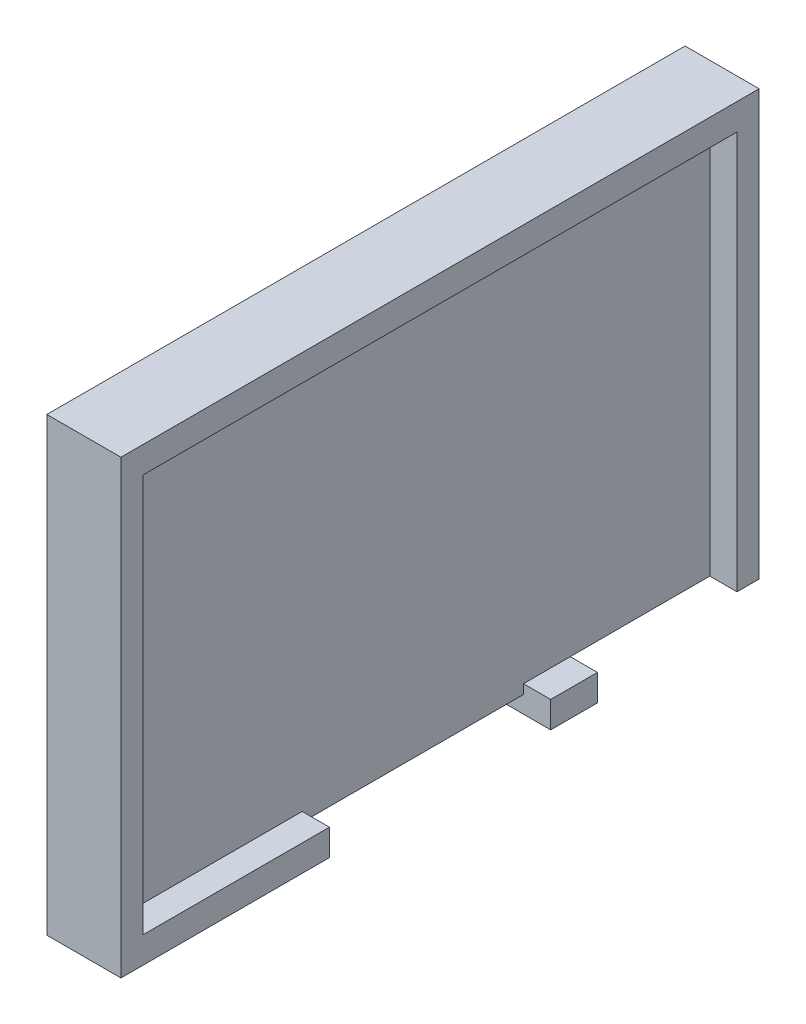
SolidWorks part; units mm, degrees
ref_plane "Front Plane" through (0, 0, 0) normal (1, 0, 0) x (0, 1, 0)
ref_plane "Top Plane" through (0, 0, 0) normal (0, 0, 1) x (0, 1, 0)
ref_plane "Right Plane" through (0, 0, 0) normal (0, 1, 0) x (-1, 0, 0)
sketch "Sketch1" plane through (0, 0, 0) normal (1, 0, 0) x (0, 1, 0)
  line L0 (42.12, 117.43) -> (42.12, 129.18) construction
  line L1 (44.62, 126.68) -> (71.12, 126.68)
  line L2 (44.62, 126.68) -> (44.62, 89.18)
  line L3 (44.62, 89.18) -> (71.12, 89.18)
  line L4 (71.12, 126.68) -> (71.12, 89.18)
  line L5 (42.12, 129.18) -> (89.12, 129.18) construction
  dimension "D1" = 26.5
  dimension "D2" = 37.5
  dimension "D3" = 2.5
  dimension "D4" = 2.5
extrude "Boss-Extrude1" add sketch "Sketch1" along normal blind 4.353 contours L2 L3 L4 L1
sketch "Sketch2" plane through (4.353, 0, 0) normal (1, 0, 0) x (0, 1, 0)
  line L0 (57.87, 126.68) -> (57.87, 89.18)
  line L1 (44.62, 126.68) -> (71.12, 126.68) construction
  line L2 (44.62, 89.18) -> (71.12, 89.18) construction
  line L3 (44.62, 107.93) -> (71.12, 107.93)
  line L4 (44.62, 126.68) -> (44.62, 89.18) construction
  line L5 (71.12, 126.68) -> (71.12, 89.18) construction
  line L7 (69.57, 90.48) -> (46.17, 90.48)
  line L8 (69.57, 90.48) -> (69.57, 125.38)
  line L9 (69.57, 125.38) -> (46.17, 125.38)
  line L10 (46.17, 90.48) -> (46.17, 125.38)
  line L11 (69.57, 90.48) -> (46.17, 125.38) construction
  line L12 (69.57, 125.38) -> (46.17, 90.48) construction
  point P12 (57.87, 107.93)
  dimension "D1" = 23.4
  dimension "D2" = 34.9
extrude "Cut-Extrude1" cut sketch "Sketch2" against normal blind 1.6 contours L7 L10 L9 L8
sketch "Sketch3" plane through (4.353, 0, 0) normal (1, 0, 0) x (0, 1, 0)
  line L0 (44.62, 107.93) -> (46.17, 107.93)
  line L1 (44.62, 126.68) -> (44.62, 89.18) construction
  line L2 (46.17, 90.48) -> (46.17, 125.38) construction
  line L3 (46.17, 125.38) -> (46.17, 126.68)
  line L4 (44.62, 126.68) -> (71.12, 126.68) construction
  line L5 (45.395, 107.93) -> (45.395, 126.68)
  line L7 (46.17, 101.43) -> (44.62, 101.43)
  line L8 (46.17, 101.43) -> (46.17, 114.43)
  line L9 (46.17, 114.43) -> (44.62, 114.43)
  line L10 (44.62, 101.43) -> (44.62, 114.43)
  line L11 (46.17, 101.43) -> (44.62, 114.43) construction
  line L12 (46.17, 114.43) -> (44.62, 101.43) construction
  dimension "D1" = 13
extrude "Cut-Extrude2" cut sketch "Sketch3" against normal blind 1.6 contours L7 L10 L9 L8
sketch "Sketch4" plane through (0, 44.62, 0) normal (0, -1, 0) x (1, 0, 0)
  line L0 (0, 126.68) -> (0, 89.18) construction
  line L1 (2.753, 101.43) -> (0, 101.43)
  line L2 (2.753, 101.43) -> (2.753, 114.43)
  line L3 (2.753, 114.43) -> (0, 114.43)
  line L4 (0, 101.43) -> (0, 114.43)
extrude "Cut-Extrude3" cut sketch "Sketch4" against normal blind 1
sketch "Sketch5" plane through (4.353, 0, 0) normal (1, 0, 0) x (0, 1, 0)
  line L0 (46.17, 90.48) -> (46.17, 101.43) construction
  line L1 (44.62, 89.18) -> (46.17, 89.18)
  line L2 (44.62, 89.18) -> (44.62, 98.68)
  line L3 (44.62, 98.68) -> (46.17, 98.68)
  line L4 (46.17, 89.18) -> (46.17, 98.68)
  dimension "D1" = 9.5
extrude "Cut-Extrude5" cut sketch "Sketch5" against normal blind 1.6 contours L2 L1 L4 L3
sketch "Sketch6" plane through (0, 0, 89.18) normal (0, 0, -1) x (1, 0, 0)
  line L0 (4.353, -46.17) -> (1.953, -46.17)
  line L1 (1.953, -46.17) -> (1.953, -49.12)
  line L2 (1.953, -49.12) -> (0, -49.12)
  line L3 (0, -44.62) -> (0, -71.12) construction
  line L4 (0, -49.12) -> (0, -44.62)
  line L5 (0, -44.62) -> (2.753, -44.62)
  line L6 (2.753, -44.62) -> (2.753, -46.17)
  line M1 (2.753, -46.17) -> (2.753, -44.62)
  line M2 (2.753, -44.62) -> (0, -44.62)
  line M3 (0, -44.62) -> (0, -71.12)
  dimension "D1" = 2.4
  dimension "D2" = 2.95
extrude "Cut-Extrude6" cut sketch "Sketch6" against normal blind 9.5 contours L2 L1 L0 M1 M2 M3 region at (1.1467, 46.6876, 89.18)
sketch "Sketch7" plane through (0, 0, 0) normal (-1, 0, 0) x (0, -1, 0)
  line L0 (-49.12, 98.68) -> (-49.12, 89.18) construction
  line L1 (-66.8403, 98.7845) -> (-56.9188, 98.7845)
  line L2 (-66.8403, 98.7845) -> (-66.8403, 116.2777)
  line L3 (-66.8403, 116.2777) -> (-56.9188, 116.2777)
  line L4 (-56.9188, 98.7845) -> (-56.9188, 116.2777)
  line L5 (-57.3291, 90.6534) -> (-49.12, 90.6534)
  line L6 (-57.3291, 90.6534) -> (-57.3291, 95.8379)
  line L7 (-57.3291, 95.8379) -> (-49.12, 95.8379)
  line L8 (-49.12, 90.6534) -> (-49.12, 95.8379)
  line L10 (-54.8301, 122.5066) -> (-50.2424, 122.5066)
  line L11 (-54.8301, 122.5066) -> (-54.8301, 95.8379)
  line L12 (-54.8301, 95.8379) -> (-50.2424, 95.8379)
  line L13 (-50.2424, 122.5066) -> (-50.2424, 95.8379)
  line M22 (-49.12, 89.18) -> (-49.12, 98.68)
extrude "Cut-Extrude7" cut sketch "Sketch7" against normal blind 2 contours L13 L10 L11 L7 | L7 L6 L5 M22 | L1 L4 L3 L2 region at (0, 61.8796, 107.5311) region at (0, 53.2246, 93.2457) region at (0, 52.5362, 109.1723)
sketch "Sketch8" plane through (0, 0, 0) normal (-1, 0, 0) x (0, -1, 0)
  line L0 (-68.22, 121.18) -> (-68.195, 94.68)
  line L1 (-67.32, 121.18) -> (-69.12, 121.18) construction
  line L2 (-69.095, 94.68) -> (-67.295, 94.68) construction
  line L3 (-68.2075, 107.93) -> (-42.7917, 107.93)
  line L4 (-67.32, 123.18) -> (-47.92, 123.18)
  line L5 (-67.32, 125.18) -> (-67.32, 121.18) construction
  line L6 (-47.92, 121.18) -> (-47.92, 125.18) construction
  line L7 (-57.62, 123.18) -> (-57.62, 84.9383)
ref_plane "Plane2" through (0, 57.62, 0) normal (0, -1, 0) x (1, 0, 0)
ref_plane "Plane3" through (0, 0, 107.93) normal (0, 0, 1) x (0, -1, 0)
sketch "Sketch10" plane through (0, 0, 0) normal (-1, 0, 0) x (0, -1, 0)
  line L0 (-67.42, 125.08) -> (-67.42, 121.28)
  line L1 (-67.32, 125.18) -> (-69.12, 125.18)
  line L2 (-67.32, 125.18) -> (-67.32, 121.18)
  line L3 (-67.32, 121.18) -> (-69.12, 121.18)
  line L4 (-69.12, 125.18) -> (-69.12, 121.18)
  line L5 (-67.42, 121.28) -> (-69.02, 121.28)
  line L6 (-69.02, 125.08) -> (-69.02, 121.28)
  line L7 (-67.42, 125.08) -> (-69.02, 125.08)
  dimension "D1" = 0.1
extrude "Boss-Extrude3" add sketch "Sketch10" along normal blind 1.6 contours L6 L5 L0 L7
mirror "Mirror1" about plane through (0, 57.62, 0) normal (0, -1, 0) of "Boss-Extrude3"
mirror "Mirror2" about plane through (0, 0, 107.93) normal (0, 0, 1) of "Boss-Extrude3"
